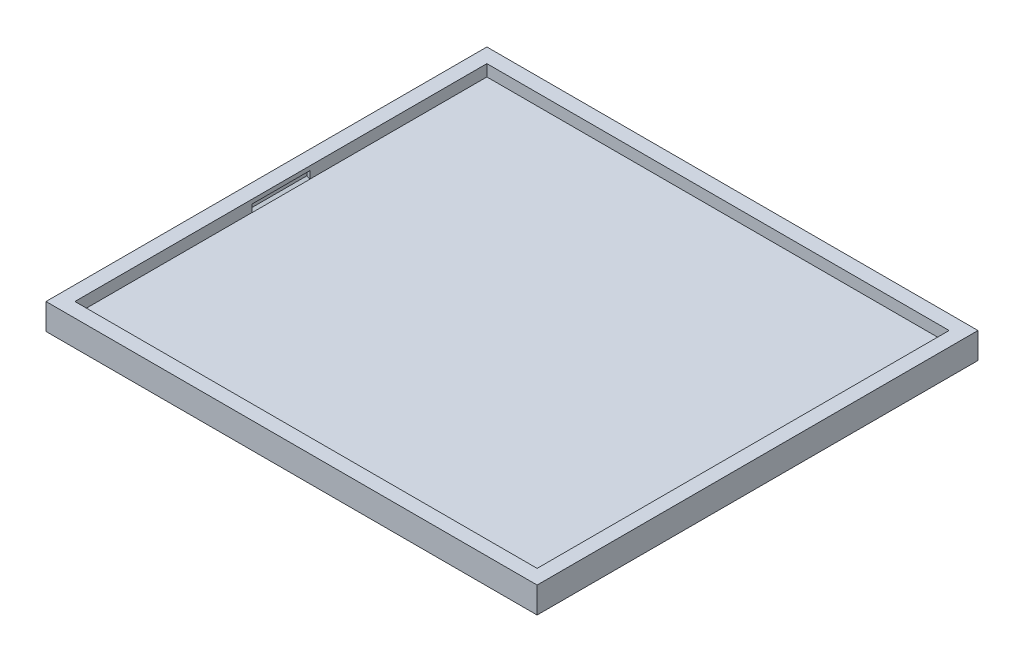
SolidWorks part; units mm, degrees
ref_plane "Front Plane" through (0, 0, 0) normal (0, 0, 1) x (1, 0, 0)
ref_plane "Top Plane" through (0, 0, 0) normal (0, 1, 0) x (1, 0, 0)
ref_plane "Right Plane" through (0, 0, 0) normal (1, 0, 0) x (0, 0, -1)
sketch "Sketch2" plane through (0, 0, 0) normal (0, 1, 0) x (1, 0, 0)
  line L0 (-0.05, -0.05) -> (203.25, -0.05)
  line L1 (0, 0) -> (203.2, 0) construction
  line L2 (0, 0) -> (0, 181.102) construction
  line L3 (0, 181.102) -> (203.2, 181.102) construction
  line L4 (203.2, 0) -> (203.2, 181.102) construction
  line L5 (203.25, -0.05) -> (203.25, 181.152)
  line L6 (-0.05, 181.152) -> (203.25, 181.152)
  line L7 (-0.05, -0.05) -> (-0.05, 181.152)
  line L9 (-6.4, 187.502) -> (209.6, 187.502)
  line L10 (-6.4, 187.502) -> (-6.4, -6.4)
  line L11 (-6.4, -6.4) -> (209.6, -6.4)
  line L12 (209.6, 187.502) -> (209.6, -6.4)
  dimension "D1" = 181.102
  dimension "D2" = 203.2
  dimension "D4" = 6.35
  dimension "D5" = 6.35
  dimension "D6" = 6.35
  dimension "D7" = 6.35
  dimension "D3" = 0.05
extrude "Boss-Extrude1" add sketch "Sketch2" along normal blind 12.7
extrude "Boss-Extrude2" add sketch "Sketch2<3>" along normal blind 6.35 contours L7 L0 L5 L6 region at (101.6, 0, -90.551)
sketch "Sketch2<3>" plane through (0, 0, 0) normal (0, 1, 0) x (1, 0, 0) same geometry as "Sketch2"
ref_plane "Plane1" through (0, 0, -90.551) normal (0, 0, -1) x (-1, 0, 0)
sketch "Sketch4" plane through (0, 0, -90.551) normal (0, 0, -1) x (-1, 0, 0)
  line L0 (-203.25, 9.525) -> (-204.4577, 8.3173) construction
  line L2 (-204.4577, 7.0473) -> (-203.25, 6.35) construction
  line L3 (-204.4577, 7.0473) -> (-204.4577, 8.3173) construction
  line L5 (-208.108, 7.6823) -> (-205.9578, 7.6823) construction
  line L6 (-209.6, 12.7) -> (-209.6, 0) construction
  line L7 (-203.2, 9.6457) -> (-204.5077, 8.338)
  line L8 (-204.5077, 7.0184) -> (-204.5077, 8.338)
  line L9 (-209.6, 12.7) -> (6.4, 12.7) construction
  line L10 (-203.25, 6.35) -> (-203.25, 9.525) construction
  line L11 (-204.5077, 7.0184) -> (-203.2, 6.2634)
  line L12 (-203.2, 6.2634) -> (-203.2, 9.6457)
  point P13 (-204.4577, 7.6823)
  dimension "D1" = 6.35
  dimension "D2" = 45
  dimension "D3" = 30
  dimension "D4" = 3.175
  dimension "D5" = 3.175
  dimension "D6" = 1.27
  dimension "D7" = 0.05
extrude "Cut-Extrude1" cut sketch "Sketch4" against normal blind 12.7 and the other way blind 12.7 contours L7 L8 L11 L12
sketch "Sketch5" plane through (0, 12.7, 0) normal (0, 1, 0) x (1, 0, 0)
  line L4 (-6.4, 187.502) -> (-6.4, -6.4)
  line L5 (-6.4, -6.4) -> (209.6, -6.4)
  line L6 (209.6, -6.4) -> (209.6, 187.502)
  line L7 (209.6, 187.502) -> (-6.4, 187.502)
  line L8 (-6.4, 187.502) -> (-6.4, -6.4)
  line L9 (-6.4, -6.4) -> (209.6, -6.4)
  line L10 (209.6, -6.4) -> (209.6, 187.502)
  line L11 (209.6, 187.502) -> (-6.4, 187.502)
  line L16 (203.2, 77.851) -> (203.2, 103.251)
  line L17 (203.2, 103.251) -> (203.25, 103.251)
  line L18 (203.25, 103.251) -> (203.25, 181.152)
  line L19 (203.25, 181.152) -> (-0.05, 181.152)
  line L20 (-0.05, 181.152) -> (-0.05, -0.05)
  line L21 (-0.05, -0.05) -> (203.25, -0.05)
  line L22 (203.25, -0.05) -> (203.25, 77.851)
  line L23 (203.25, 77.851) -> (203.2, 77.851)
  line L24 (203.2, 77.851) -> (203.2, 103.251)
  line L25 (203.2, 103.251) -> (203.25, 103.251)
  line L26 (203.25, 103.251) -> (203.25, 181.152)
  line L27 (203.25, 181.152) -> (-0.05, 181.152)
  line L28 (-0.05, 181.152) -> (-0.05, -0.05)
  line L29 (-0.05, -0.05) -> (203.25, -0.05)
  line L30 (203.25, -0.05) -> (203.25, 77.851)
  line L31 (203.25, 77.851) -> (203.2, 77.851)
  dimension "D1" = 0
  dimension "D2" = 0
extrude "Cut-Extrude2" cut sketch "Sketch5" against normal blind 1.27
ref_plane "Plane3" through (101.6, 0, 0) normal (-1, 0, 0) x (0, 0, 1)
mirror "Mirror1" about plane through (101.6, 0, 0) normal (-1, 0, 0) of "Cut-Extrude1"
